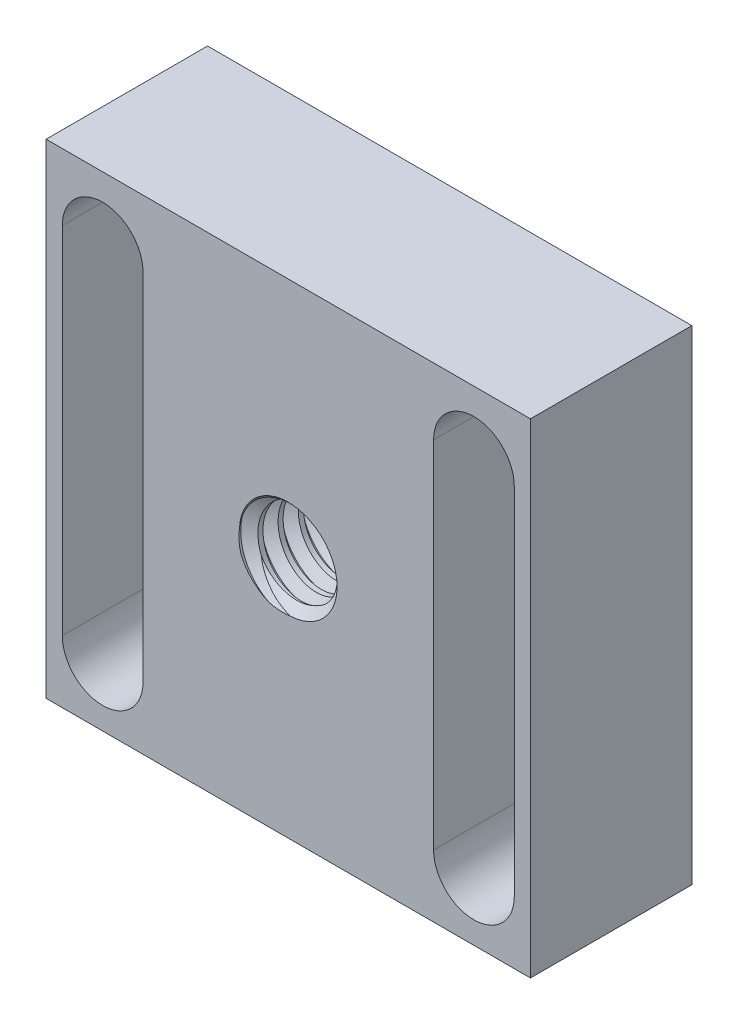
SolidWorks part; units mm, degrees
ref_plane "前视基准面" through (0, 0, 0) normal (0, 0, 1) x (1, 0, 0)
ref_plane "上视基准面" through (0, 0, 0) normal (0, 1, 0) x (1, 0, 0)
ref_plane "右视基准面" through (0, 0, 0) normal (1, 0, 0) x (0, 0, -1)
other "Configuration Table"
sketch "草图1" plane through (0, 0, 0) normal (0, 0, 1) x (1, 0, 0)
  line L1 (-15, 15) -> (15, 15)
  line L2 (-15, 15) -> (-15, -15)
  line L3 (-15, -15) -> (15, -15)
  line L4 (15, 15) -> (15, -15)
  line L5 (-15, 15) -> (15, -15) construction
  line L6 (-15, -15) -> (15, 15) construction
  point P0 (0, 0)
  dimension "D1" = 30
  dimension "D2" = 30
extrude "凸台-拉伸1" add sketch "草图1" against normal blind 10
sketch "草图5" plane through (0, 0, 0) normal (0, 0, 1) x (1, 0, 0)
  line L0 (-15, 15) -> (-15, -15) construction
  line L2 (-14, 10.8705) -> (-14, -11.1295)
  line L4 (-9, 10.8705) -> (-9, -11.1295)
  arc A0 (-9, 10.8705) -> (-14, 10.8705) centre (-11.5, 10.8705) ccw
  arc A1 (-14, -11.1295) -> (-9, -11.1295) centre (-11.5, -11.1295) ccw
  dimension "D4" = 5
  dimension "D1" = 5
  dimension "D2" = 1
  dimension "D3" = 22
extrude "切除-拉伸1" cut sketch "草图5" against normal blind 150
mirror "镜向1" about plane through (0, 0, 0) normal (1, 0, 0) of "切除-拉伸1"
sketch "草图9" plane through (0, 0, 0) normal (0, 1, 0) x (1, 0, 0)
  line L2 (8, 8) -> (8, 10)
  line L4 (8, 10) -> (6.5, 10)
  line L5 (8, 8) -> (6.5, 8)
  line L6 (6.5, 8) -> (6.5, 10)
  line L7 (15, 10) -> (-15, 10) construction
  line L8 (0, 0) -> (0, 10)
  point P0 (6.5, 9)
  dimension "D1" = 8
  dimension "D2" = 2
  dimension "D3" = 6.5
  dimension "D4" = 0
revolve "切除-旋转1" cut sketch "草图9" angle 360 about L8
hole_wizard "M6 螺纹孔2" positions "3D草图1" profile "草图10" tap size "M6" standard "GB"
sketch3d "3D草图1"
  point P0 (0, 0, 0)
  dimension "D1" = 0
sketch "草图10" plane through (0, 0, 0) normal (1, 0, 0) x (0, -1, 0)
  line L0 (0, 0) -> (0, 11.5022)
  line L1 (0, 11.5022) -> (2.5, 10)
  line L2 (2.5, 10) -> (2.5, 0.525)
  line L3 (2.5, 0.525) -> (3.025, 0)
  line L5 (3.025, 0) -> (0, 0)
  line L6 (-2.5, 0.525) -> (-3.025, 0) construction
  line L10 (0, 11.5022) -> (-2.5, 10) construction
  line L11 (0, -6.35) -> (0, 107.95) construction
  dimension "螺纹孔钻头直径" = 5
  dimension "螺纹孔钻头深度" = 10
  dimension "近端锥形沉头孔直径" = 6.05
  dimension "近端锥形沉头孔角度" = 90
  dimension "导头角度" = 118
cosmetic thread "孔螺纹线35" parameters "D1"=10, "D2"=6
thread "螺纹线1" pitch 1.25 method cut profile "螺纹线轮廓1" start angle 0, offset 0, length 10, pitch 1.25, diameter 5
ref_plane "基准面1" through (2.5, 0, -10) normal (0, -1, 0) x (1, 0, 0)
sketch "螺纹线轮廓1" plane through (2.5, 0, -10) normal (0, -1, 0) x (1, 0, 0)
  line L0 (0, 0) -> (0, 1.25) construction
  line L1 (0, 0) -> (0.6766, 0.3906)
  line L2 (0.6766, 0.3906) -> (0.6766, 0.5469)
  line L3 (0.6766, 0.5469) -> (0, 0.9375)
  line L4 (0.6766, 0.4687) -> (0, 0.4687) construction
  line L11 (0, 0) -> (0, 0.9375)
  point P2 (0, 0)
  dimension "Pitch" = 1.25
  dimension "Profile_Angle" = 60
  dimension "Profile_Land" = 0.1562
  dimension "Profile_Height" = 0.6766
